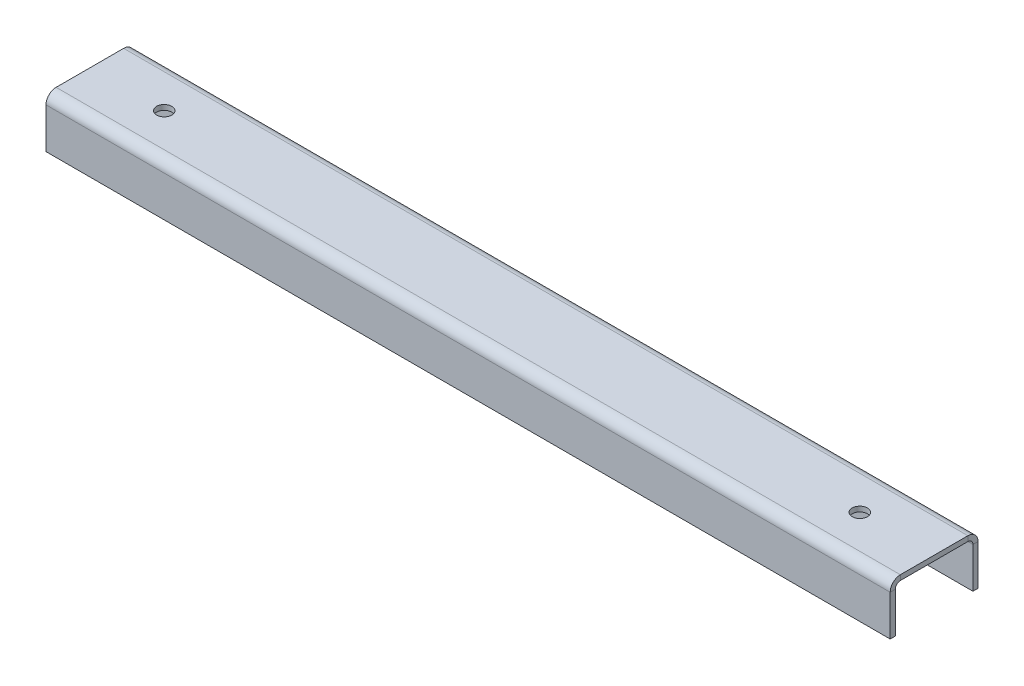
SolidWorks part; units mm, degrees
note: The reader was unsure of these and kept them because the rebuilt part matched: flange length of "Edge-Flange1".
ref_plane "Front Plane" through (0, 0, 0) normal (0, 0, 1) x (1, 0, 0)
ref_plane "Top Plane" through (0, 0, 0) normal (0, 1, 0) x (1, 0, 0)
ref_plane "Right Plane" through (0, 0, 0) normal (1, 0, 0) x (0, 0, -1)
sketch "Sketch1" plane through (1355.3234, -102522.5636, -30605.1084) normal (0, 1, 0) x (1, 0, 0)
  line L1 (-249.6317, -1685.0336) -> (250.3683, -1685.0336)
  line L2 (-249.6317, -1685.0336) -> (-249.6317, -1725.0336)
  line L3 (-249.6317, -1725.0336) -> (250.3683, -1725.0336)
  line L4 (250.3683, -1685.0336) -> (250.3683, -1725.0336)
  circle A0 centre (-205.6317, -1705.0336) radius 4.5
  circle A1 centre (206.3683, -1705.0336) radius 4.5
  dimension "D3" = 9
  dimension "D4" = 9
  dimension "D5" = 412
  dimension "D6" = 44
  dimension "D1" = 40
  dimension "D2" = 500
  dimension "D7" = 44
base flange "Base-Flange1" sketch "Sketch1" thickness 3 reverse thickness direction no parameters "D1"=0.7366
edge flange "Edge-Flange1" sketch "Sketch10" flange profiles "Sketch10", "Sketch11" flange angle 90 flange length 30 flange position bend outside bend radius 3 thickness 3 relief rectangular parameters "D6"=10, "D8"=1
sketch "Sketch10" plane through (0, -102525.5636, -28880.0748) normal (0, 0, 1) x (-1, 0, 0)
  line L2 (-1605.6917, 0) -> (-1605.6917, 27)
  line L3 (-1605.6917, 27) -> (-1105.6917, 27)
  line L4 (-1105.6917, 27) -> (-1105.6917, 0)
  line L7 (-1105.6917, 0) -> (-1605.6917, 0) construction
  line L8 (-1105.6917, 0) -> (-1605.6917, 0)
sketch "Sketch11" plane through (0, -102525.5636, -28920.0748) normal (0, 0, -1) x (1, 0, 0)
  line L0 (1605.6917, 0) -> (1105.6917, 0) construction
  line L1 (1605.6917, 0) -> (1105.6917, 0)
  line L2 (1105.6917, 0) -> (1105.6917, 27)
  line L3 (1105.6917, 27) -> (1605.6917, 27)
  line L4 (1605.6917, 27) -> (1605.6917, 0)
bend "EdgeBend1" bend radius 3 bend angle 90 parameters "D5"=1
bend "EdgeBend2" bend radius 3 bend angle 90 parameters "D5"=2
sketch "Bend-Lines1" [suppressed] plane through (0, 0, 0) normal (0, 1, 0) x (1, 0, 0)
sketch "Bounding-Box1" [suppressed] plane through (0, 0, 0) normal (0, 1, 0) x (1, 0, 0)
sheet metal parameters "Sheet-Metal1" thickness 3 parameters "D1"=0.7366
flat pattern "Flat-Pattern1" [suppressed]
sketch "Bend-Lines2" plane through (0, 0, 0) normal (0, 1, 0) x (1, 0, 0)
sketch3d "Bounding-Box2" [suppressed]
  line L0 (-250.3683, -1725.0336, 0) -> (249.6317, -1725.0336, 0) construction
  line L1 (-250.3683, -1685.0336, 0) -> (249.6317, -1685.0336, 0) construction
  line L2 (-250.3683, -1725.0336, 0) -> (-250.3683, -1685.0336, 0) construction
  line L3 (249.6317, -1725.0336, 0) -> (249.6317, -1685.0336, 0) construction
sheet metal parameters "Sheet-Metal2" thickness 3 parameters "D1"=0.7366
flat pattern "Flat-Pattern1" [suppressed]
sketch "Bend-Lines2" plane through (0, -102522.5636, 0) normal (0, 1, 0) x (1, 0, 0)
  line L0 (1605.6917, 28923.3735) -> (1105.6917, 28923.3735) construction
  line L1 (1105.6917, 28876.7762) -> (1605.6917, 28876.7762) construction
  line L2 (1605.6917, 28923.3735) -> (1105.6917, 28923.3735) construction
  line L3 (1105.6917, 28876.7762) -> (1605.6917, 28876.7762) construction
sketch3d "Bounding-Box2" [suppressed]
  line L0 (1605.6917, 28849.4775, 0) -> (1105.6917, 28849.4775, 0) construction
  line L1 (1605.6917, 28950.6722, 0) -> (1105.6917, 28950.6722, 0) construction
  line L2 (1605.6917, 28849.4775, 0) -> (1605.6917, 28950.6722, 0) construction
  line L3 (1105.6917, 28849.4775, 0) -> (1105.6917, 28950.6722, 0) construction
bend of the flat pattern "Flatten-<EdgeBend1>1"
bend of the flat pattern "Flatten-<EdgeBend2>1"
